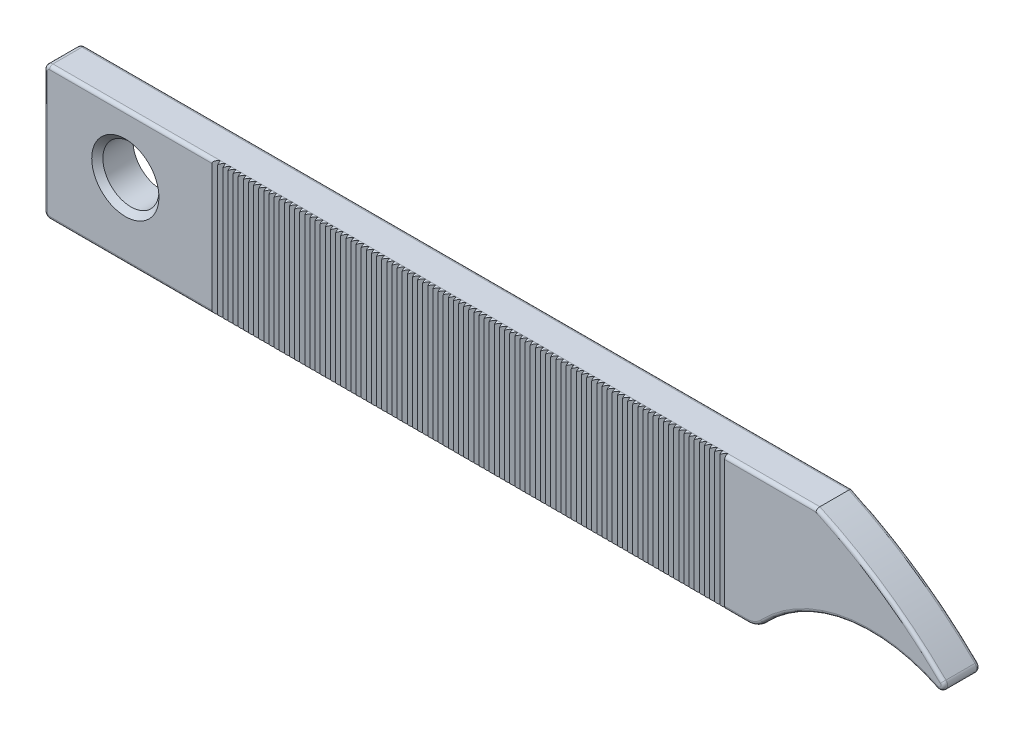
SolidWorks part; units mm, degrees
ref_plane "Płaszczyzna przednia" through (0, 0, 0) normal (0, 0, 1) x (1, 0, 0)
ref_plane "Płaszczyzna górna" through (0, 0, 0) normal (0, 1, 0) x (1, 0, 0)
ref_plane "Płaszczyzna prawa" through (0, 0, 0) normal (1, 0, 0) x (0, 0, -1)
sketch "Sketch1" plane through (0, 0, 0) normal (0, 0, 1) x (1, 0, 0)
  line L0 (-1.5855, 0) -> (-33.5855, 0)
  line L1 (-33.5855, 0) -> (-33.5855, 6)
  line L2 (-33.5855, 6) -> (1.0944, 6)
  arc A2 (1.0944, 6) -> (8.4145, 0.25) centre (-7.2608, -12.1712) cw
  arc A3 (-1.5855, 0) -> (8.4145, 0.25) centre (3.5254, -4.3096) cw
  point P8 (-13.7084, 6)
  point P9 (-4.1291, 6)
  point P10 (0, 0)
  point P11 (0, 0)
  point P12 (-5.3564, 6)
  point P13 (0, 0)
  point P14 (1.6698, 6)
  point P15 (5.264, 6)
  point P16 (-0.4272, 6)
  point P17 (-6.4518, 6)
  point P18 (-10.1382, 6)
  point P19 (1.0944, 6)
  point P20 (0, 0)
  point P21 (0, 0)
  dimension "D5" = 20
  dimension "D1" = 6
  dimension "D2" = 42
  dimension "D3" = 32
  dimension "D4" = 5.75
extrude "Boss-Extrude2" add sketch "Sketch1" along normal blind 1.6
fillet "Fillet1" radius 1 1 edges at (-1.5855, 0, 0.8)
fillet "Fillet2" radius 0.25 1 edges at (8.4145, 0.25, 0.8)
fillet "Fillet3" radius 0.25 2 edges at (-33.5855, 0, 0.8) (-33.5855, 6, 0.8)
fillet "Fillet4" radius 0.15 18 edges at (4.0949, 4.2924, 0) (6.7858, 1.7714, 0) (2.3558, 2.2726, 0) (-1.6378, 0.0805, 0) (-17.6832, 0, 0) (-33.5123, 0.0732, 0) (-33.5855, 3, 0) (-33.5123, 5.9268, 0) (4.0949, 4.2924, 1.6) (6.7858, 1.7714, 1.6) (2.3558, 2.2726, 1.6) (-1.6378, 0.0805, 1.6) (-17.6832, 0, 1.6) (-33.5123, 0.0732, 1.6) (-33.5855, 3, 1.6) (-33.5123, 5.9268, 1.6) (-16.1206, 6, 0) (-16.1206, 6, 1.6)
sketch "Sketch2" plane through (0, 0, 1.6) normal (0, 0, 1) x (1, 0, 0)
  line L0 (-33.4355, 5.75) -> (-33.4355, 0.25) construction
  line L1 (-33.3355, 0.15) -> (-2.0309, 0.15) construction
  circle A0 centre (-29.9355, 3.35) radius 1.259
  dimension "D1" = 2.5179
  dimension "D2" = 3.5
  dimension "D3" = 3.2
extrude "Cut-Extrude1" cut sketch "Sketch2" against normal through all contours A0
chamfer "Chamfer1" distance 0.25 angle 45 1 edges at (-28.6765, 3.35, 1.6)
sketch "Sketch3" plane through (0, 0, 0) normal (0, -1, 0) x (1, 0, 0)
  line L0 (-3.2809, 1.6) -> (-3.0309, 1.45)
  line L1 (-33.3355, 1.6) -> (-2.0309, 1.6) construction
  line L2 (-2.0309, 1.45) -> (-33.3355, 1.45) construction
  line L3 (-3.0309, 1.45) -> (-3.0309, 1.6)
  line L4 (-2.0309, 1.6) -> (-2.0309, 1.45) construction
  point P6 (0, 0)
  point P8 (0, 0)
  dimension "D1" = 0.25
  dimension "D2" = 1
extrude "Cut-Extrude2" cut sketch "Sketch3" against normal through all and the other way through all
pattern_linear "LPattern1" count 100 spacing 0.23 along (-1, 0, 0) of "Cut-Extrude2"
